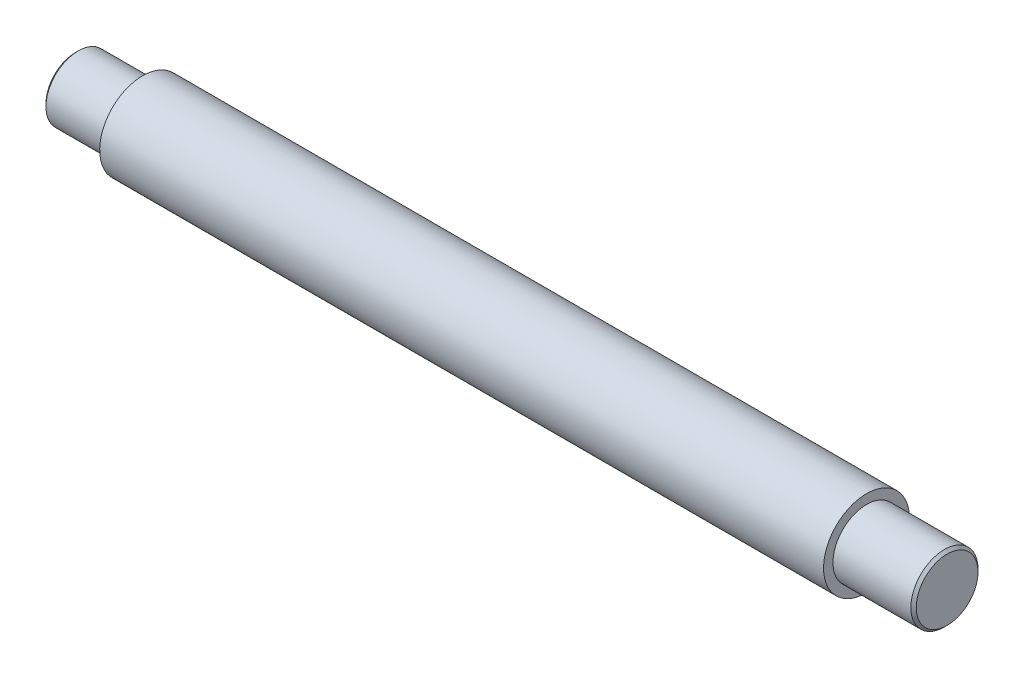
SolidWorks part; units mm, degrees
ref_plane "Plan de face" through (0, 0, 0) normal (0, 0, 1) x (1, 0, 0)
ref_plane "Plan de dessus" through (0, 0, 0) normal (0, 1, 0) x (1, 0, 0)
ref_plane "Plan de droite" through (0, 0, 0) normal (1, 0, 0) x (0, 0, -1)
sketch "Esquisse2" plane through (0, 370.9997, -115.2031) normal (0, -0.955, 0.2966) x (1, 0, 0)
  line L0 (-27.8836, 210.7104) -> (263.8964, 210.7104) construction
  line L1 (311.4618, 222.2104) -> (311.4618, 210.7104)
  line L2 (310.4618, 223.2104) -> (311.4618, 222.2104)
  line L4 (12, 226.7104) -> (12, 222.7104)
  line L5 (12, 226.7104) -> (281.4618, 226.7104)
  line L6 (12, 222.7104) -> (-13, 222.7104)
  line L7 (-13, 222.7104) -> (-13, 210.7104)
  line L12 (281.4618, 226.7104) -> (281.4618, 223.2104)
  line L13 (281.4618, 223.2104) -> (310.4618, 223.2104)
  line L17 (-13, 210.7104) -> (311.4618, 210.7104)
  point P18 (311.4618, 223.2104)
  dimension "D1" = 25
  dimension "D2" = 12
  dimension "D3" = 30
  dimension "D4" = 16
revolve "Révolution1" add sketch "Esquisse2" angle 360 about L0
ref_axis "Axe1" through (310.9079, 433.4864, 86.0288) along (-1, 0, 0)
ref_plane "Plan1" through (0, 433.4864, 0) normal (0, 1, 0) x (-1, 0, 0)
ref_plane "Plan2" through (0, 421.4864, 0) normal (0, 1, 0) x (-1, 0, 0)
sketch "Esquisse3" plane through (0, 421.4864, 0) normal (0, 1, 0) x (-1, 0, 0)
  line L0 (-207.9618, 86.0288) -> (-195.9618, 86.0288) construction
  line L1 (-310.9079, 86.0288) -> (-150.5311, 86.0288) construction
  line L2 (-207.9618, 90.0288) -> (-195.9618, 90.0288)
  line L3 (-207.9618, 82.0288) -> (-195.9618, 82.0288)
  line L4 (-51.9618, 86.0288) -> (-39.9618, 86.0288) construction
  line L5 (-51.9618, 90.0288) -> (-39.9618, 90.0288)
  line L6 (-51.9618, 82.0288) -> (-39.9618, 82.0288)
  line L7 (-281.4618, 102.0288) -> (-281.4618, 70.0288) construction
  arc A0 (-207.9618, 90.0288) -> (-207.9618, 82.0288) centre (-207.9618, 86.0288) ccw
  arc A1 (-195.9618, 82.0288) -> (-195.9618, 90.0288) centre (-195.9618, 86.0288) ccw
  arc A2 (-51.9618, 90.0288) -> (-51.9618, 82.0288) centre (-51.9618, 86.0288) ccw
  arc A3 (-39.9618, 82.0288) -> (-39.9618, 90.0288) centre (-39.9618, 86.0288) ccw
  point P4 (-201.9618, 86.0288)
  point P9 (-45.9618, 86.0288)
  dimension "D1" = 12
  dimension "D2" = 8
  dimension "D3" = 12
  dimension "D4" = 8
  dimension "D5" = 73.5
  dimension "D6" = 144
extrude "Enlèv. mat.-Extru.1" cut sketch "Esquisse3" against normal blind 10
ref_plane "Plan3" through (0, 51.951, -104.1977) normal (0, -0.4462, 0.8949) x (-1, 0, 0)
sketch "Esquisse4" plane through (0, 55.9668, -112.2521) normal (0, -0.4462, 0.8949) x (-1, 0, 0)
  line L0 (-305.4618, -426.3277) -> (-287.4618, -426.3277) construction
  line L1 (-305.4618, -423.3277) -> (-287.4618, -423.3277)
  line L2 (-305.4618, -429.3277) -> (-287.4618, -429.3277)
  line L3 (-311.4618, -414.8277) -> (-311.4618, -437.8277) construction
  line L4 (-310.9079, -426.3277) -> (-150.5311, -426.3277) construction
  arc A0 (-305.4618, -423.3277) -> (-305.4618, -429.3277) centre (-305.4618, -426.3277) ccw
  arc A1 (-287.4618, -429.3277) -> (-287.4618, -423.3277) centre (-287.4618, -426.3277) ccw
  point P2 (-296.4618, -426.3277)
  dimension "D1" = 6
  dimension "D2" = 18
  dimension "D3" = 6
extrude "Enlèv. mat.-Extru.2" cut sketch "Esquisse4" against normal blind 48
chamfer "Chanfrein1" distance 1 angle 45 1 edges at (-13, 421.4864, 86.0288)
